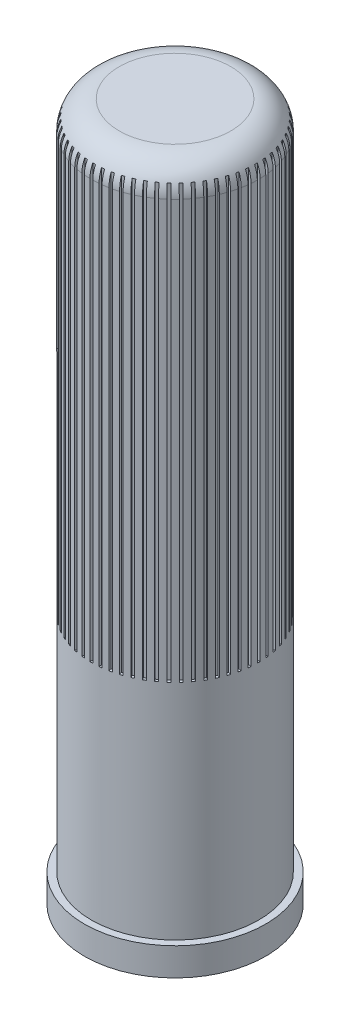
SolidWorks part; units mm, degrees
ref_plane "Front Plane" through (0, 0, 0) normal (0, 0, 1) x (1, 0, 0)
ref_plane "Top Plane" through (0, 0, 0) normal (0, 1, 0) x (1, 0, 0)
ref_plane "Right Plane" through (0, 0, 0) normal (1, 0, 0) x (0, 0, -1)
sketch "Sketch1" plane through (0, 0, 0) normal (0, 1, 0) x (1, 0, 0)
  circle A0 centre (0, 0) radius 3.25
  dimension "D1" = 6.5
extrude "Boss-Extrude1" add sketch "Sketch1" along normal blind 25
sketch "Sketch2" plane through (0, 25, 0) normal (0, 1, 0) x (1, 0, 0)
  circle A0 centre (0, 0) radius 4.5665
  circle A1 centre (0, 0) radius 3
  dimension "D1" = 6
extrude "Cut-Extrude1" cut sketch "Sketch2" against normal blind 24
fillet "Fillet1" radius 1 1 edges at (0, 25, 3)
sketch "Sketch3" plane through (0, 25, 0) normal (0, 1, 0) x (1, 0, 0)
  line L0 (0, 2.9) -> (0, 3) construction
  line L1 (0.05, 2.9) -> (0.05, 3)
  line L2 (-0.05, 2.9) -> (-0.05, 3)
  line L3 (-0.05, 2.9) -> (0.05, 2.9)
  line L4 (0.05, 0) -> (0.05, 3) construction
  line L5 (0, 0) -> (0, 3) construction
  line L6 (-0.05, 0) -> (-0.05, 3) construction
  line L7 (0.3529, 2.8789) -> (0.3633, 2.9783)
  line L8 (0.2534, 2.8893) -> (0.2639, 2.9888)
  line L9 (0.2534, 2.8893) -> (0.3529, 2.8789)
  line L10 (0.3031, 2.8841) -> (0.3136, 2.9836) construction
  line L11 (0.6519, 2.8262) -> (0.6726, 2.924)
  line L12 (0.554, 2.847) -> (0.5748, 2.9448)
  line L13 (0.554, 2.847) -> (0.6519, 2.8262)
  line L14 (0.6029, 2.8366) -> (0.6237, 2.9344) construction
  line L15 (0.9437, 2.7426) -> (0.9746, 2.8377)
  line L16 (0.8486, 2.7735) -> (0.8795, 2.8686)
  line L17 (0.8486, 2.7735) -> (0.9437, 2.7426)
  line L18 (0.8961, 2.7581) -> (0.9271, 2.8532) construction
  line L19 (1.2252, 2.6289) -> (1.2659, 2.7203)
  line L20 (1.1339, 2.6696) -> (1.1745, 2.761)
  line L21 (1.1339, 2.6696) -> (1.2252, 2.6289)
  line L22 (1.1795, 2.6493) -> (1.2202, 2.7406) construction
  line L23 (1.4933, 2.4865) -> (1.5433, 2.5731)
  line L24 (1.4067, 2.5365) -> (1.4567, 2.6231)
  line L25 (1.4067, 2.5365) -> (1.4933, 2.4865)
  line L26 (1.45, 2.5115) -> (1.5, 2.5981) construction
  line L27 (1.745, 2.3168) -> (1.8038, 2.3977)
  line L28 (1.6641, 2.3755) -> (1.7229, 2.4564)
  line L29 (1.6641, 2.3755) -> (1.745, 2.3168)
  line L30 (1.7046, 2.3461) -> (1.7634, 2.4271) construction
  line L31 (1.9776, 2.1217) -> (2.0445, 2.196)
  line L32 (1.9033, 2.1886) -> (1.9702, 2.2629)
  line L33 (1.9033, 2.1886) -> (1.9776, 2.1217)
  line L34 (1.9405, 2.1551) -> (2.0074, 2.2294) construction
  line L35 (2.1886, 1.9033) -> (2.2629, 1.9702)
  line L36 (2.1217, 1.9776) -> (2.196, 2.0445)
  line L37 (2.1217, 1.9776) -> (2.1886, 1.9033)
  line L38 (2.1551, 1.9405) -> (2.2294, 2.0074) construction
  line L39 (2.3755, 1.6641) -> (2.4564, 1.7229)
  line L40 (2.3168, 1.745) -> (2.3977, 1.8038)
  line L41 (2.3168, 1.745) -> (2.3755, 1.6641)
  line L42 (2.3461, 1.7046) -> (2.4271, 1.7634) construction
  line L43 (2.5365, 1.4067) -> (2.6231, 1.4567)
  line L44 (2.4865, 1.4933) -> (2.5731, 1.5433)
  line L45 (2.4865, 1.4933) -> (2.5365, 1.4067)
  line L46 (2.5115, 1.45) -> (2.5981, 1.5) construction
  line L47 (2.6696, 1.1339) -> (2.761, 1.1745)
  line L48 (2.6289, 1.2252) -> (2.7203, 1.2659)
  line L49 (2.6289, 1.2252) -> (2.6696, 1.1339)
  line L50 (2.6493, 1.1795) -> (2.7406, 1.2202) construction
  line L51 (2.7735, 0.8486) -> (2.8686, 0.8795)
  line L52 (2.7426, 0.9437) -> (2.8377, 0.9746)
  line L53 (2.7426, 0.9437) -> (2.7735, 0.8486)
  line L54 (2.7581, 0.8961) -> (2.8532, 0.9271) construction
  line L55 (2.847, 0.554) -> (2.9448, 0.5748)
  line L56 (2.8262, 0.6519) -> (2.924, 0.6726)
  line L57 (2.8262, 0.6519) -> (2.847, 0.554)
  line L58 (2.8366, 0.6029) -> (2.9344, 0.6237) construction
  line L59 (2.8893, 0.2534) -> (2.9888, 0.2639)
  line L60 (2.8789, 0.3529) -> (2.9783, 0.3633)
  line L61 (2.8789, 0.3529) -> (2.8893, 0.2534)
  line L62 (2.8841, 0.3031) -> (2.9836, 0.3136) construction
  line L63 (2.9, -0.05) -> (3, -0.05)
  line L64 (2.9, 0.05) -> (3, 0.05)
  line L65 (2.9, 0.05) -> (2.9, -0.05)
  line L66 (2.9, 0) -> (3, 0) construction
  line L67 (2.8789, -0.3529) -> (2.9783, -0.3633)
  line L68 (2.8893, -0.2534) -> (2.9888, -0.2639)
  line L69 (2.8893, -0.2534) -> (2.8789, -0.3529)
  line L70 (2.8841, -0.3031) -> (2.9836, -0.3136) construction
  line L71 (2.8262, -0.6519) -> (2.924, -0.6726)
  line L72 (2.847, -0.554) -> (2.9448, -0.5748)
  line L73 (2.847, -0.554) -> (2.8262, -0.6519)
  line L74 (2.8366, -0.6029) -> (2.9344, -0.6237) construction
  line L75 (2.7426, -0.9437) -> (2.8377, -0.9746)
  line L76 (2.7735, -0.8486) -> (2.8686, -0.8795)
  line L77 (2.7735, -0.8486) -> (2.7426, -0.9437)
  line L78 (2.7581, -0.8961) -> (2.8532, -0.9271) construction
  line L79 (2.6289, -1.2252) -> (2.7203, -1.2659)
  line L80 (2.6696, -1.1339) -> (2.761, -1.1745)
  line L81 (2.6696, -1.1339) -> (2.6289, -1.2252)
  line L82 (2.6493, -1.1795) -> (2.7406, -1.2202) construction
  line L83 (2.4865, -1.4933) -> (2.5731, -1.5433)
  line L84 (2.5365, -1.4067) -> (2.6231, -1.4567)
  line L85 (2.5365, -1.4067) -> (2.4865, -1.4933)
  line L86 (2.5115, -1.45) -> (2.5981, -1.5) construction
  line L87 (2.3168, -1.745) -> (2.3977, -1.8038)
  line L88 (2.3755, -1.6641) -> (2.4564, -1.7229)
  line L89 (2.3755, -1.6641) -> (2.3168, -1.745)
  line L90 (2.3461, -1.7046) -> (2.4271, -1.7634) construction
  line L91 (2.1217, -1.9776) -> (2.196, -2.0445)
  line L92 (2.1886, -1.9033) -> (2.2629, -1.9702)
  line L93 (2.1886, -1.9033) -> (2.1217, -1.9776)
  line L94 (2.1551, -1.9405) -> (2.2294, -2.0074) construction
  line L95 (1.9033, -2.1886) -> (1.9702, -2.2629)
  line L96 (1.9776, -2.1217) -> (2.0445, -2.196)
  line L97 (1.9776, -2.1217) -> (1.9033, -2.1886)
  line L98 (1.9405, -2.1551) -> (2.0074, -2.2294) construction
  line L99 (1.6641, -2.3755) -> (1.7229, -2.4564)
  line L100 (1.745, -2.3168) -> (1.8038, -2.3977)
  line L101 (1.745, -2.3168) -> (1.6641, -2.3755)
  line L102 (1.7046, -2.3461) -> (1.7634, -2.4271) construction
  line L103 (1.4067, -2.5365) -> (1.4567, -2.6231)
  line L104 (1.4933, -2.4865) -> (1.5433, -2.5731)
  line L105 (1.4933, -2.4865) -> (1.4067, -2.5365)
  line L106 (1.45, -2.5115) -> (1.5, -2.5981) construction
  line L107 (1.1339, -2.6696) -> (1.1745, -2.761)
  line L108 (1.2252, -2.6289) -> (1.2659, -2.7203)
  line L109 (1.2252, -2.6289) -> (1.1339, -2.6696)
  line L110 (1.1795, -2.6493) -> (1.2202, -2.7406) construction
  line L111 (0.8486, -2.7735) -> (0.8795, -2.8686)
  line L112 (0.9437, -2.7426) -> (0.9746, -2.8377)
  line L113 (0.9437, -2.7426) -> (0.8486, -2.7735)
  line L114 (0.8961, -2.7581) -> (0.9271, -2.8532) construction
  line L115 (0.554, -2.847) -> (0.5748, -2.9448)
  line L116 (0.6519, -2.8262) -> (0.6726, -2.924)
  line L117 (0.6519, -2.8262) -> (0.554, -2.847)
  line L118 (0.6029, -2.8366) -> (0.6237, -2.9344) construction
  line L119 (0.2534, -2.8893) -> (0.2639, -2.9888)
  line L120 (0.3529, -2.8789) -> (0.3633, -2.9783)
  line L121 (0.3529, -2.8789) -> (0.2534, -2.8893)
  line L122 (0.3031, -2.8841) -> (0.3136, -2.9836) construction
  line L123 (-0.05, -2.9) -> (-0.05, -3)
  line L124 (0.05, -2.9) -> (0.05, -3)
  line L125 (0.05, -2.9) -> (-0.05, -2.9)
  line L126 (0, -2.9) -> (0, -3) construction
  line L127 (-0.3529, -2.8789) -> (-0.3633, -2.9783)
  line L128 (-0.2534, -2.8893) -> (-0.2639, -2.9888)
  line L129 (-0.2534, -2.8893) -> (-0.3529, -2.8789)
  line L130 (-0.3031, -2.8841) -> (-0.3136, -2.9836) construction
  line L131 (-0.6519, -2.8262) -> (-0.6726, -2.924)
  line L132 (-0.554, -2.847) -> (-0.5748, -2.9448)
  line L133 (-0.554, -2.847) -> (-0.6519, -2.8262)
  line L134 (-0.6029, -2.8366) -> (-0.6237, -2.9344) construction
  line L135 (-0.9437, -2.7426) -> (-0.9746, -2.8377)
  line L136 (-0.8486, -2.7735) -> (-0.8795, -2.8686)
  line L137 (-0.8486, -2.7735) -> (-0.9437, -2.7426)
  line L138 (-0.8961, -2.7581) -> (-0.9271, -2.8532) construction
  line L139 (-1.2252, -2.6289) -> (-1.2659, -2.7203)
  line L140 (-1.1339, -2.6696) -> (-1.1745, -2.761)
  line L141 (-1.1339, -2.6696) -> (-1.2252, -2.6289)
  line L142 (-1.1795, -2.6493) -> (-1.2202, -2.7406) construction
  line L143 (-1.4933, -2.4865) -> (-1.5433, -2.5731)
  line L144 (-1.4067, -2.5365) -> (-1.4567, -2.6231)
  line L145 (-1.4067, -2.5365) -> (-1.4933, -2.4865)
  line L146 (-1.45, -2.5115) -> (-1.5, -2.5981) construction
  line L147 (-1.745, -2.3168) -> (-1.8038, -2.3977)
  line L148 (-1.6641, -2.3755) -> (-1.7229, -2.4564)
  line L149 (-1.6641, -2.3755) -> (-1.745, -2.3168)
  line L150 (-1.7046, -2.3461) -> (-1.7634, -2.4271) construction
  line L151 (-1.9776, -2.1217) -> (-2.0445, -2.196)
  line L152 (-1.9033, -2.1886) -> (-1.9702, -2.2629)
  line L153 (-1.9033, -2.1886) -> (-1.9776, -2.1217)
  line L154 (-1.9405, -2.1551) -> (-2.0074, -2.2294) construction
  line L155 (-2.1886, -1.9033) -> (-2.2629, -1.9702)
  line L156 (-2.1217, -1.9776) -> (-2.196, -2.0445)
  line L157 (-2.1217, -1.9776) -> (-2.1886, -1.9033)
  line L158 (-2.1551, -1.9405) -> (-2.2294, -2.0074) construction
  line L159 (-2.3755, -1.6641) -> (-2.4564, -1.7229)
  line L160 (-2.3168, -1.745) -> (-2.3977, -1.8038)
  line L161 (-2.3168, -1.745) -> (-2.3755, -1.6641)
  line L162 (-2.3461, -1.7046) -> (-2.4271, -1.7634) construction
  line L163 (-2.5365, -1.4067) -> (-2.6231, -1.4567)
  line L164 (-2.4865, -1.4933) -> (-2.5731, -1.5433)
  line L165 (-2.4865, -1.4933) -> (-2.5365, -1.4067)
  line L166 (-2.5115, -1.45) -> (-2.5981, -1.5) construction
  line L167 (-2.6696, -1.1339) -> (-2.761, -1.1745)
  line L168 (-2.6289, -1.2252) -> (-2.7203, -1.2659)
  line L169 (-2.6289, -1.2252) -> (-2.6696, -1.1339)
  line L170 (-2.6493, -1.1795) -> (-2.7406, -1.2202) construction
  line L171 (-2.7735, -0.8486) -> (-2.8686, -0.8795)
  line L172 (-2.7426, -0.9437) -> (-2.8377, -0.9746)
  line L173 (-2.7426, -0.9437) -> (-2.7735, -0.8486)
  line L174 (-2.7581, -0.8961) -> (-2.8532, -0.9271) construction
  line L175 (-2.847, -0.554) -> (-2.9448, -0.5748)
  line L176 (-2.8262, -0.6519) -> (-2.924, -0.6726)
  line L177 (-2.8262, -0.6519) -> (-2.847, -0.554)
  line L178 (-2.8366, -0.6029) -> (-2.9344, -0.6237) construction
  line L179 (-2.8893, -0.2534) -> (-2.9888, -0.2639)
  line L180 (-2.8789, -0.3529) -> (-2.9783, -0.3633)
  line L181 (-2.8789, -0.3529) -> (-2.8893, -0.2534)
  line L182 (-2.8841, -0.3031) -> (-2.9836, -0.3136) construction
  line L183 (-2.9, 0.05) -> (-3, 0.05)
  line L184 (-2.9, -0.05) -> (-3, -0.05)
  line L185 (-2.9, -0.05) -> (-2.9, 0.05)
  line L186 (-2.9, 0) -> (-3, 0) construction
  line L187 (-2.8789, 0.3529) -> (-2.9783, 0.3633)
  line L188 (-2.8893, 0.2534) -> (-2.9888, 0.2639)
  line L189 (-2.8893, 0.2534) -> (-2.8789, 0.3529)
  line L190 (-2.8841, 0.3031) -> (-2.9836, 0.3136) construction
  line L191 (-2.8262, 0.6519) -> (-2.924, 0.6726)
  line L192 (-2.847, 0.554) -> (-2.9448, 0.5748)
  line L193 (-2.847, 0.554) -> (-2.8262, 0.6519)
  line L194 (-2.8366, 0.6029) -> (-2.9344, 0.6237) construction
  line L195 (-2.7426, 0.9437) -> (-2.8377, 0.9746)
  line L196 (-2.7735, 0.8486) -> (-2.8686, 0.8795)
  line L197 (-2.7735, 0.8486) -> (-2.7426, 0.9437)
  line L198 (-2.7581, 0.8961) -> (-2.8532, 0.9271) construction
  line L199 (-2.6289, 1.2252) -> (-2.7203, 1.2659)
  line L200 (-2.6696, 1.1339) -> (-2.761, 1.1745)
  line L201 (-2.6696, 1.1339) -> (-2.6289, 1.2252)
  line L202 (-2.6493, 1.1795) -> (-2.7406, 1.2202) construction
  line L203 (-2.4865, 1.4933) -> (-2.5731, 1.5433)
  line L204 (-2.5365, 1.4067) -> (-2.6231, 1.4567)
  line L205 (-2.5365, 1.4067) -> (-2.4865, 1.4933)
  line L206 (-2.5115, 1.45) -> (-2.5981, 1.5) construction
  line L207 (-2.3168, 1.745) -> (-2.3977, 1.8038)
  line L208 (-2.3755, 1.6641) -> (-2.4564, 1.7229)
  line L209 (-2.3755, 1.6641) -> (-2.3168, 1.745)
  line L210 (-2.3461, 1.7046) -> (-2.4271, 1.7634) construction
  line L211 (-2.1217, 1.9776) -> (-2.196, 2.0445)
  line L212 (-2.1886, 1.9033) -> (-2.2629, 1.9702)
  line L213 (-2.1886, 1.9033) -> (-2.1217, 1.9776)
  line L214 (-2.1551, 1.9405) -> (-2.2294, 2.0074) construction
  line L215 (-1.9033, 2.1886) -> (-1.9702, 2.2629)
  line L216 (-1.9776, 2.1217) -> (-2.0445, 2.196)
  line L217 (-1.9776, 2.1217) -> (-1.9033, 2.1886)
  line L218 (-1.9405, 2.1551) -> (-2.0074, 2.2294) construction
  line L219 (-1.6641, 2.3755) -> (-1.7229, 2.4564)
  line L220 (-1.745, 2.3168) -> (-1.8038, 2.3977)
  line L221 (-1.745, 2.3168) -> (-1.6641, 2.3755)
  line L222 (-1.7046, 2.3461) -> (-1.7634, 2.4271) construction
  line L223 (-1.4067, 2.5365) -> (-1.4567, 2.6231)
  line L224 (-1.4933, 2.4865) -> (-1.5433, 2.5731)
  line L225 (-1.4933, 2.4865) -> (-1.4067, 2.5365)
  line L226 (-1.45, 2.5115) -> (-1.5, 2.5981) construction
  line L227 (-1.1339, 2.6696) -> (-1.1745, 2.761)
  line L228 (-1.2252, 2.6289) -> (-1.2659, 2.7203)
  line L229 (-1.2252, 2.6289) -> (-1.1339, 2.6696)
  line L230 (-1.1795, 2.6493) -> (-1.2202, 2.7406) construction
  line L231 (-0.8486, 2.7735) -> (-0.8795, 2.8686)
  line L232 (-0.9437, 2.7426) -> (-0.9746, 2.8377)
  line L233 (-0.9437, 2.7426) -> (-0.8486, 2.7735)
  line L234 (-0.8961, 2.7581) -> (-0.9271, 2.8532) construction
  line L235 (-0.554, 2.847) -> (-0.5748, 2.9448)
  line L236 (-0.6519, 2.8262) -> (-0.6726, 2.924)
  line L237 (-0.6519, 2.8262) -> (-0.554, 2.847)
  line L238 (-0.6029, 2.8366) -> (-0.6237, 2.9344) construction
  line L239 (-0.2534, 2.8893) -> (-0.2639, 2.9888)
  line L240 (-0.3529, 2.8789) -> (-0.3633, 2.9783)
  line L241 (-0.3529, 2.8789) -> (-0.2534, 2.8893)
  line L242 (-0.3031, 2.8841) -> (-0.3136, 2.9836) construction
  circle A0 centre (0, 0) radius 3 construction
  arc A1 (0.05, 2.9996) -> (-0.05, 2.9996) centre (0, 0) ccw
  arc A2 (0.3633, 2.9779) -> (0.2638, 2.9884) centre (0, 0) ccw
  arc A3 (0.6726, 2.9236) -> (0.5747, 2.9444) centre (0, 0) ccw
  arc A4 (0.9745, 2.8373) -> (0.8794, 2.8682) centre (0, 0) ccw
  arc A5 (1.2657, 2.7199) -> (1.1744, 2.7606) centre (0, 0) ccw
  arc A6 (1.5431, 2.5727) -> (1.4565, 2.6227) centre (0, 0) ccw
  arc A7 (1.8036, 2.3973) -> (1.7227, 2.4561) centre (0, 0) ccw
  arc A8 (2.0443, 2.1957) -> (1.97, 2.2626) centre (0, 0) ccw
  arc A9 (2.2626, 1.97) -> (2.1957, 2.0443) centre (0, 0) ccw
  arc A10 (2.4561, 1.7227) -> (2.3973, 1.8036) centre (0, 0) ccw
  arc A11 (2.6227, 1.4565) -> (2.5727, 1.5431) centre (0, 0) ccw
  arc A12 (2.7606, 1.1744) -> (2.7199, 1.2657) centre (0, 0) ccw
  arc A13 (2.8682, 0.8794) -> (2.8373, 0.9745) centre (0, 0) ccw
  arc A14 (2.9444, 0.5747) -> (2.9236, 0.6726) centre (0, 0) ccw
  arc A15 (2.9884, 0.2638) -> (2.9779, 0.3633) centre (0, 0) ccw
  arc A16 (2.9996, -0.05) -> (2.9996, 0.05) centre (0, 0) ccw
  arc A17 (2.9779, -0.3633) -> (2.9884, -0.2638) centre (0, 0) ccw
  arc A18 (2.9236, -0.6726) -> (2.9444, -0.5747) centre (0, 0) ccw
  arc A19 (2.8373, -0.9745) -> (2.8682, -0.8794) centre (0, 0) ccw
  arc A20 (2.7199, -1.2657) -> (2.7606, -1.1744) centre (0, 0) ccw
  arc A21 (2.5727, -1.5431) -> (2.6227, -1.4565) centre (0, 0) ccw
  arc A22 (2.3973, -1.8036) -> (2.4561, -1.7227) centre (0, 0) ccw
  arc A23 (2.1957, -2.0443) -> (2.2626, -1.97) centre (0, 0) ccw
  arc A24 (1.97, -2.2626) -> (2.0443, -2.1957) centre (0, 0) ccw
  arc A25 (1.7227, -2.4561) -> (1.8036, -2.3973) centre (0, 0) ccw
  arc A26 (1.4565, -2.6227) -> (1.5431, -2.5727) centre (0, 0) ccw
  arc A27 (1.1744, -2.7606) -> (1.2657, -2.7199) centre (0, 0) ccw
  arc A28 (0.8794, -2.8682) -> (0.9745, -2.8373) centre (0, 0) ccw
  arc A29 (0.5747, -2.9444) -> (0.6726, -2.9236) centre (0, 0) ccw
  arc A30 (0.2638, -2.9884) -> (0.3633, -2.9779) centre (0, 0) ccw
  arc A31 (-0.05, -2.9996) -> (0.05, -2.9996) centre (0, 0) ccw
  arc A32 (-0.3633, -2.9779) -> (-0.2638, -2.9884) centre (0, 0) ccw
  arc A33 (-0.6726, -2.9236) -> (-0.5747, -2.9444) centre (0, 0) ccw
  arc A34 (-0.9745, -2.8373) -> (-0.8794, -2.8682) centre (0, 0) ccw
  arc A35 (-1.2657, -2.7199) -> (-1.1744, -2.7606) centre (0, 0) ccw
  arc A36 (-1.5431, -2.5727) -> (-1.4565, -2.6227) centre (0, 0) ccw
  arc A37 (-1.8036, -2.3973) -> (-1.7227, -2.4561) centre (0, 0) ccw
  arc A38 (-2.0443, -2.1957) -> (-1.97, -2.2626) centre (0, 0) ccw
  arc A39 (-2.2626, -1.97) -> (-2.1957, -2.0443) centre (0, 0) ccw
  arc A40 (-2.4561, -1.7227) -> (-2.3973, -1.8036) centre (0, 0) ccw
  arc A41 (-2.6227, -1.4565) -> (-2.5727, -1.5431) centre (0, 0) ccw
  arc A42 (-2.7606, -1.1744) -> (-2.7199, -1.2657) centre (0, 0) ccw
  arc A43 (-2.8682, -0.8794) -> (-2.8373, -0.9745) centre (0, 0) ccw
  arc A44 (-2.9444, -0.5747) -> (-2.9236, -0.6726) centre (0, 0) ccw
  arc A45 (-2.9884, -0.2638) -> (-2.9779, -0.3633) centre (0, 0) ccw
  arc A46 (-2.9996, 0.05) -> (-2.9996, -0.05) centre (0, 0) ccw
  arc A47 (-2.9779, 0.3633) -> (-2.9884, 0.2638) centre (0, 0) ccw
  arc A48 (-2.9236, 0.6726) -> (-2.9444, 0.5747) centre (0, 0) ccw
  arc A49 (-2.8373, 0.9745) -> (-2.8682, 0.8794) centre (0, 0) ccw
  arc A50 (-2.7199, 1.2657) -> (-2.7606, 1.1744) centre (0, 0) ccw
  arc A51 (-2.5727, 1.5431) -> (-2.6227, 1.4565) centre (0, 0) ccw
  arc A52 (-2.3973, 1.8036) -> (-2.4561, 1.7227) centre (0, 0) ccw
  arc A53 (-2.1957, 2.0443) -> (-2.2626, 1.97) centre (0, 0) ccw
  arc A54 (-1.97, 2.2626) -> (-2.0443, 2.1957) centre (0, 0) ccw
  arc A55 (-1.7227, 2.4561) -> (-1.8036, 2.3973) centre (0, 0) ccw
  arc A56 (-1.4565, 2.6227) -> (-1.5431, 2.5727) centre (0, 0) ccw
  arc A57 (-1.1744, 2.7606) -> (-1.2657, 2.7199) centre (0, 0) ccw
  arc A58 (-0.8794, 2.8682) -> (-0.9745, 2.8373) centre (0, 0) ccw
  arc A59 (-0.5747, 2.9444) -> (-0.6726, 2.9236) centre (0, 0) ccw
  arc A60 (-0.2638, 2.9884) -> (-0.3633, 2.9779) centre (0, 0) ccw
  point P489 (0, 0)
  dimension "D3" = 0.1
  dimension "D1" = 0.05
  dimension "D2" = 0.1
  dimension "D4" = 60
extrude "Cut-Extrude2" cut sketch "Sketch3" against normal blind 16 contours L191 A48 L192 L193 | L195 A49 L196 L197 | L199 A50 L200 L201 | L203 A51 L204 L205 | L187 A47 L188 L189 | L183 A46 L184 L185 | L179 A45 L180 L181 | L175 A44 L176 L177 | L171 A43 L172 L173 | L167 A42 L168 L169 | L163 A41 L164 L165 | L159 A40 L160 L161 | L155 A39 L156 L157 | L151 A38 L152 L153 | L147 A37 L148 L149 | L143 A36 L144 L145 | L139 A35 L140 L141 | L135 A34 L136 L137 | L131 A33 L132 L133 | L127 A32 L128 L129 | L123 A31 L124 L125 | L119 A30 L120 L121 | L115 A29 L116 L117 | L111 A28 L112 L113 | L107 A27 L108 L109 | L103 A26 L104 L105 | L99 A25 L100 L101 | L95 A24 L96 L97 | L91 A23 L92 L93 | L87 A22 L88 L89 | L83 A21 L84 L85 | L79 A20 L80 L81 | L75 A19 L76 L77 | L71 A18 L72 L73 | L67 A17 L68 L69 | L63 A16 L64 L65 | L59 A15 L60 L61 | L51 A13 L52 L53 | L55 A14 L56 L57 | L47 A12 L48 L49 | L43 A11 L44 L45 | L39 A10 L40 L41 | L35 A9 L36 L37 | L31 A8 L32 L33 | L27 A7 L28 L29 | L23 A6 L24 L25 | L19 A5 L20 L21 | L15 A4 L16 L17 | L11 A3 L12 L13 | L7 A2 L8 L9 | L207 A52 L208 L209 | L211 A53 L212 L213 | L215 A54 L216 L217 | L219 A55 L220 L221 | L223 A56 L224 L225 | L227 A57 L228 L229 | L231 A58 L232 L233 | L235 A59 L236 L237 | L239 A60 L240 L241 | L1 A1 L2 L3 region at (0, 25, -2.9499) region at (0.3084, 25, -2.9338) region at (0.6133, 25, -2.8855) region at (0.9116, 25, -2.8056) region at (1.1998, 25, -2.6949) region at (1.475, 25, -2.5547) region at (1.7339, 25, -2.3865) region at (1.9739, 25, -2.1922) region at (2.1922, 25, -1.9739) region at (2.3865, 25, -1.7339) region at (2.5547, 25, -1.475) region at (2.6949, 25, -1.1998) region at (2.8056, 25, -0.9116) region at (2.8855, 25, -0.6133) region at (2.9338, 25, -0.3084) region at (2.9499, 25, 0) region at (2.9338, 25, 0.3084) region at (2.8855, 25, 0.6133) region at (2.8056, 25, 0.9116) region at (2.6949, 25, 1.1998) region at (2.5547, 25, 1.475) region at (2.3865, 25, 1.7339) region at (2.1922, 25, 1.9739) region at (1.9739, 25, 2.1922) region at (1.7339, 25, 2.3865) region at (1.475, 25, 2.5547) region at (1.1998, 25, 2.6949) region at (0.9116, 25, 2.8056) region at (0.6133, 25, 2.8855) region at (0.3084, 25, 2.9338) region at (0, 25, 2.9499) region at (-0.3084, 25, 2.9338) region at (-0.6133, 25, 2.8855) region at (-0.9116, 25, 2.8056) region at (-1.1998, 25, 2.6949) region at (-1.475, 25, 2.5547) region at (-1.7339, 25, 2.3865) region at (-1.9739, 25, 2.1922) region at (-2.1922, 25, 1.9739) region at (-2.3865, 25, 1.7339) region at (-2.5547, 25, 1.475) region at (-2.6949, 25, 1.1998) region at (-2.8056, 25, 0.9116) region at (-2.8855, 25, 0.6133) region at (-2.9338, 25, 0.3084) region at (-2.9499, 25, 0) region at (-2.9338, 25, -0.3084) region at (-2.8855, 25, -0.6133) region at (-2.8056, 25, -0.9116) region at (-2.6949, 25, -1.1998) region at (-2.5547, 25, -1.475) region at (-2.3865, 25, -1.7339) region at (-2.1922, 25, -1.9739) region at (-1.9739, 25, -2.1922) region at (-1.7339, 25, -2.3865) region at (-1.475, 25, -2.5547) region at (-1.1998, 25, -2.6949) region at (-0.9116, 25, -2.8056) region at (-0.6133, 25, -2.8855) region at (-0.3084, 25, -2.9338)
